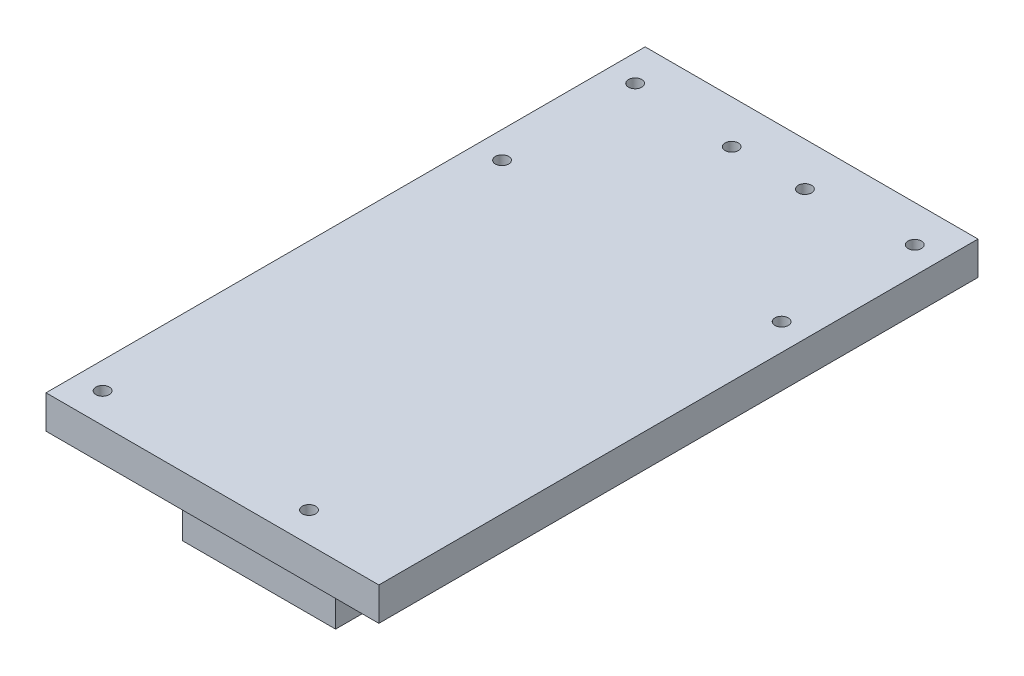
SolidWorks part; units mm, degrees
ref_plane "Front Plane" through (0, 0, 0) normal (0, 0, 1) x (1, 0, 0)
ref_plane "Top Plane" through (0, 0, 0) normal (0, 1, 0) x (1, 0, 0)
ref_plane "Right Plane" through (0, 0, 0) normal (1, 0, 0) x (0, 0, -1)
sketch "Sketch1" plane through (0, 0, 0) normal (0, 1, 0) x (1, 0, 0)
  line L1 (-25, 45) -> (25, 45)
  line L2 (-25, 45) -> (-25, -45)
  line L3 (-25, -45) -> (25, -45)
  line L4 (25, 45) -> (25, -45)
  line L5 (-25, 45) -> (25, -45) construction
  line L6 (-25, -45) -> (25, 45) construction
  point P0 (0, 0)
  dimension "D1" = 90
  dimension "D2" = 50
extrude "Boss-Extrude1" add sketch "Sketch1" along normal blind 5
sketch "Sketch2" plane through (0, 5, 0) normal (0, 1, 0) x (1, 0, 0)
  line L0 (25, -45) -> (25, 45) construction
  line L9 (16, 42) -> (26, 42) construction
  line L11 (16, 42) -> (16, 17) construction
  line L12 (16, 17) -> (26, 17) construction
  line L13 (26, 42) -> (26, 17) construction
  line L14 (25, 45) -> (-25, 45) construction
  line L15 (26, 29.5) -> (16, 29.5) construction
  line L16 (0, 0) -> (0, 45) construction
  line L17 (0, 0) -> (0, -45) construction
  line L18 (-25, -45) -> (25, -45) construction
  circle A4 centre (21, 39.5) radius 1
  circle A5 centre (21, 19.5) radius 1
  circle A6 centre (-21, 19.5) radius 1
  circle A7 centre (-21, 39.5) radius 1
  circle A8 centre (10, -40.5) radius 1
  circle A10 centre (-21, -40.5) radius 1
  circle A11 centre (-5.5, 38.5) radius 1
  circle A12 centre (5.5, 38.5) radius 1
  point P9 (21, 39.5)
  point P10 (21, 42)
  point P25 (10, -40.5)
  dimension "D4" = 3
  dimension "D6" = 2
  dimension "D9" = 2
  dimension "D12" = 5.5
  dimension "D1" = 10
  dimension "D2" = 25
  dimension "D3" = 9
  dimension "D5" = 2.5
  dimension "D7" = 10
  dimension "D8" = 4.5
  dimension "D10" = 31
  dimension "D11" = 6.5
extrude "Cut-Extrude1" cut sketch "Sketch2" against normal through all
sketch "Sketch3" plane through (0, 0, 0) normal (0, -1, 0) x (1, 0, 0)
  line L0 (-25, 45) -> (25, 45) construction
  line L1 (-11.5, 38) -> (11.5, 38)
  line L2 (-11.5, 38) -> (-11.5, 30)
  line L3 (-11.5, 30) -> (11.5, 30)
  line L4 (11.5, 38) -> (11.5, 30)
  line L5 (-11.5, 38) -> (11.5, 30) construction
  line L6 (-11.5, 30) -> (11.5, 38) construction
  line L7 (0, 34) -> (0, 30) construction
  line L8 (-7.5, 34) -> (7.5, 34) construction
  circle A0 centre (7.5, 34) radius 1
  circle A1 centre (-7.5, 34) radius 1
  circle A2 centre (-21, 40.5) radius 1 construction
  point P0 (0, 34)
  point P7 (0, 38)
  point P14 (0, 34)
  dimension "D1" = 7
  dimension "D2" = 23
  dimension "D3" = 8
  dimension "D4" = 15
extrude "Boss-Extrude2" add sketch "Sketch3" along normal blind 11
